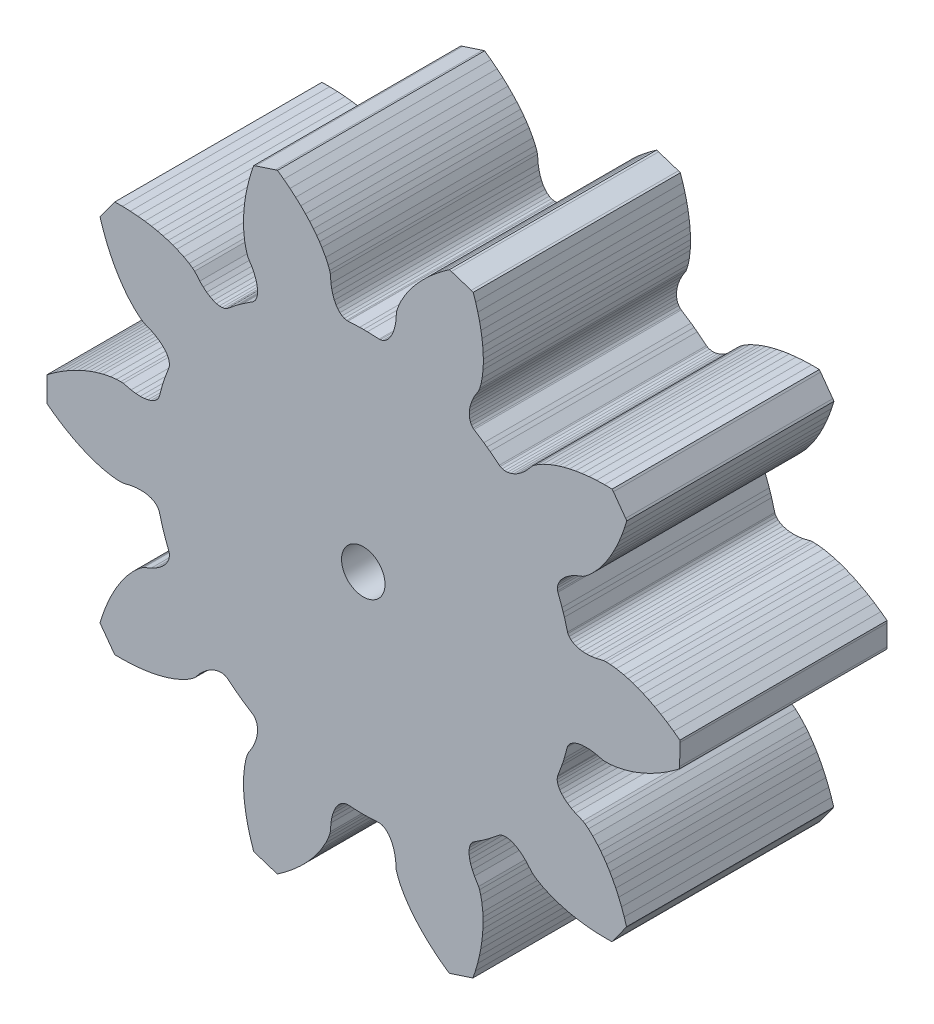
SolidWorks part; units mm, degrees
ref_plane "Front Plane" through (0, 0, 0) normal (0, 0, 1) x (1, 0, 0)
ref_plane "Top Plane" through (0, 0, 0) normal (0, 1, 0) x (1, 0, 0)
ref_plane "Right Plane" through (0, 0, 0) normal (1, 0, 0) x (0, 0, -1)
sketch "Sketch2" plane through (0, 0, 0) normal (0, 0, 1) x (1, 0, 0)
  line L40 (2.1996, 28.3978) -> (2.6736, 28.0849)
  line L41 (2.1445, 11.1227) -> (2.1761, 11.1489)
  line L42 (2.1761, 11.1489) -> (2.1872, 11.1558)
  line L43 (-3.1458, 20.8269) -> (-3.1458, 18.7268) construction
  line L699 (-2.0958, 19.7768) -> (-2.0958, 19.5922) construction
  line L700 (-2.0958, 19.5922) -> (-2.4045, 19.0354) construction
  line L701 (-2.4045, 19.0354) -> (-2.9612, 18.7268) construction
  line L702 (-2.9612, 18.7268) -> (-3.1458, 18.7268) construction
  line L703 (-3.1458, 18.7268) -> (-3.3319, 18.7268) construction
  line L704 (-3.3319, 18.7268) -> (-3.8886, 19.0354) construction
  line L705 (-3.8886, 19.0354) -> (-4.1959, 19.5922) construction
  line L706 (-4.1959, 19.5922) -> (-4.1959, 19.7768) construction
  line L707 (-4.1959, 19.7768) -> (-4.1959, 19.9628) construction
  line L708 (-4.1959, 19.9628) -> (-3.8886, 20.5196) construction
  line L709 (-3.8886, 20.5196) -> (-3.3319, 20.8269) construction
  line L710 (-3.3319, 20.8269) -> (-3.1458, 20.8269) construction
  line L711 (-3.1458, 20.8269) -> (-2.9612, 20.8269) construction
  line L712 (-2.9612, 20.8269) -> (-2.4045, 20.5196) construction
  line L713 (-2.4045, 20.5196) -> (-2.0958, 19.9628) construction
  line L714 (-2.0958, 19.9628) -> (-2.0958, 19.7768) construction
  line L715 (9.572, 28.2627) -> (9.4604, 27.9073)
  line L716 (9.4604, 27.9073) -> (9.3309, 27.5489)
  line L717 (9.3309, 27.5489) -> (9.1945, 27.2141)
  line L718 (9.1945, 27.2141) -> (9.0538, 26.9068)
  line L719 (9.0538, 26.9068) -> (8.9077, 26.6215)
  line L720 (8.9077, 26.6215) -> (8.7617, 26.3625)
  line L721 (8.7617, 26.3625) -> (8.6144, 26.1254)
  line L722 (8.6144, 26.1254) -> (8.4696, 25.9132)
  line L723 (8.4696, 25.9132) -> (8.3291, 25.723)
  line L724 (8.3291, 25.723) -> (8.194, 25.5563)
  line L725 (8.194, 25.5563) -> (7.9433, 25.2834)
  line L726 (7.9433, 25.2834) -> (7.731, 25.0878)
  line L727 (7.731, 25.0878) -> (7.5684, 24.961)
  line L728 (7.5684, 24.961) -> (7.4638, 24.8921)
  line L729 (7.4638, 24.8921) -> (7.1082, 24.746)
  line L730 (7.1082, 24.746) -> (6.9029, 24.6385)
  line L731 (6.9029, 24.6385) -> (6.7236, 24.5214)
  line L732 (6.7236, 24.5214) -> (6.572, 24.4001)
  line L733 (6.572, 24.4001) -> (6.448, 24.2747)
  line L734 (6.448, 24.2747) -> (6.3515, 24.148)
  line L735 (6.3515, 24.148) -> (6.2814, 24.0226)
  line L736 (6.2814, 24.0226) -> (6.2387, 23.8985)
  line L737 (6.2387, 23.8985) -> (6.2235, 23.7814)
  line L738 (6.2235, 23.7814) -> (6.2331, 23.6698)
  line L739 (6.2331, 23.6698) -> (6.2481, 23.6174)
  line L740 (6.2481, 23.6174) -> (6.244, 23.6298)
  line L741 (6.244, 23.6298) -> (6.2481, 23.616)
  line L742 (6.2481, 23.616) -> (6.4467, 23.0854)
  line L743 (6.4467, 23.0854) -> (6.5059, 22.9091)
  line L744 (6.5059, 22.9091) -> (6.5623, 22.7327)
  line L745 (6.5623, 22.7327) -> (6.7127, 22.1843)
  line L746 (6.7127, 22.1843) -> (6.7167, 22.1718)
  line L747 (6.7167, 22.1718) -> (6.7139, 22.1843)
  line L748 (6.7139, 22.1843) -> (6.732, 22.1333)
  line L749 (6.732, 22.1333) -> (6.7899, 22.0382)
  line L750 (6.7899, 22.0382) -> (6.8724, 21.9514)
  line L751 (6.8724, 21.9514) -> (6.9786, 21.8769)
  line L752 (6.9786, 21.8769) -> (7.1094, 21.8163)
  line L753 (7.1094, 21.8163) -> (7.2626, 21.7695)
  line L754 (7.2626, 21.7695) -> (7.4361, 21.7419)
  line L755 (7.4361, 21.7419) -> (7.6304, 21.7322)
  line L756 (7.6304, 21.7322) -> (7.8427, 21.7433)
  line L757 (7.8427, 21.7433) -> (8.0741, 21.7763)
  line L758 (8.0741, 21.7763) -> (8.4475, 21.8673)
  line L759 (8.4475, 21.8673) -> (8.5717, 21.8728)
  line L760 (8.5717, 21.8728) -> (8.7769, 21.8659)
  line L761 (8.7769, 21.8659) -> (9.0637, 21.8328)
  line L762 (9.0637, 21.8328) -> (9.4274, 21.7598)
  line L763 (9.4274, 21.7598) -> (9.6342, 21.7033)
  line L764 (9.6342, 21.7033) -> (9.86, 21.6331)
  line L765 (9.86, 21.6331) -> (10.1026, 21.5462)
  line L766 (10.1026, 21.5462) -> (10.3604, 21.4415)
  line L767 (10.3604, 21.4415) -> (10.6319, 21.3175)
  line L768 (10.6319, 21.3175) -> (10.9171, 21.1714)
  line L769 (10.9171, 21.1714) -> (11.212, 21.006)
  line L770 (11.212, 21.006) -> (11.5191, 20.8158)
  line L771 (11.5191, 20.8158) -> (11.8336, 20.6023)
  line L772 (11.8336, 20.6023) -> (12.1338, 20.3804)
  line L773 (12.1338, 20.3804) -> (12.1366, 20.2798)
  line L774 (12.1366, 20.2798) -> (12.1242, 19.2752)
  line L775 (12.1242, 19.2752) -> (12.1214, 19.1746)
  line L776 (12.1214, 19.1746) -> (11.8212, 18.9514)
  line L777 (11.8212, 18.9514) -> (11.5067, 18.7378)
  line L778 (11.5067, 18.7378) -> (11.1996, 18.5476)
  line L779 (11.1996, 18.5476) -> (10.9047, 18.3822)
  line L780 (10.9047, 18.3822) -> (10.6195, 18.2361)
  line L781 (10.6195, 18.2361) -> (10.348, 18.1135)
  line L782 (10.348, 18.1135) -> (10.0902, 18.0074)
  line L783 (10.0902, 18.0074) -> (9.8476, 17.9206)
  line L784 (9.8476, 17.9206) -> (9.6218, 17.8503)
  line L785 (9.6218, 17.8503) -> (9.415, 17.7952)
  line L786 (9.415, 17.7952) -> (9.0513, 17.7208)
  line L787 (9.0513, 17.7208) -> (8.7645, 17.6877)
  line L788 (8.7645, 17.6877) -> (8.5593, 17.6808)
  line L789 (8.5593, 17.6808) -> (8.4351, 17.6863)
  line L790 (8.4351, 17.6863) -> (8.0617, 17.7773)
  line L791 (8.0617, 17.7773) -> (7.8303, 17.8104)
  line L792 (7.8303, 17.8104) -> (7.618, 17.8214)
  line L793 (7.618, 17.8214) -> (7.4237, 17.8117)
  line L794 (7.4237, 17.8117) -> (7.2502, 17.7842)
  line L795 (7.2502, 17.7842) -> (7.097, 17.7387)
  line L796 (7.097, 17.7387) -> (6.9662, 17.6767)
  line L797 (6.9662, 17.6767) -> (6.86, 17.6023)
  line L798 (6.86, 17.6023) -> (6.7775, 17.5168)
  line L799 (6.7775, 17.5168) -> (6.7196, 17.4203)
  line L800 (6.7196, 17.4203) -> (6.7015, 17.3694)
  line L801 (6.7015, 17.3694) -> (6.7043, 17.3818)
  line L802 (6.7043, 17.3818) -> (6.7003, 17.3694)
  line L803 (6.7003, 17.3694) -> (6.5499, 16.8223)
  line L804 (6.5499, 16.8223) -> (6.4935, 16.6445)
  line L805 (6.4935, 16.6445) -> (6.4343, 16.4695)
  line L806 (6.4343, 16.4695) -> (6.2357, 15.9376)
  line L807 (6.2357, 15.9376) -> (6.2316, 15.9238)
  line L808 (6.2316, 15.9238) -> (6.2357, 15.9362)
  line L809 (6.2357, 15.9362) -> (6.2207, 15.8852)
  line L810 (6.2207, 15.8852) -> (6.2111, 15.7736)
  line L811 (6.2111, 15.7736) -> (6.2263, 15.6551)
  line L812 (6.2263, 15.6551) -> (6.269, 15.5311)
  line L813 (6.269, 15.5311) -> (6.3391, 15.4057)
  line L814 (6.3391, 15.4057) -> (6.4356, 15.2789)
  line L815 (6.4356, 15.2789) -> (6.5596, 15.1535)
  line L816 (6.5596, 15.1535) -> (6.7112, 15.0322)
  line L817 (6.7112, 15.0322) -> (6.8905, 14.9165)
  line L818 (6.8905, 14.9165) -> (7.0958, 14.8076)
  line L819 (7.0958, 14.8076) -> (7.4514, 14.6615)
  line L820 (7.4514, 14.6615) -> (7.556, 14.5926)
  line L821 (7.556, 14.5926) -> (7.7186, 14.4658)
  line L822 (7.7186, 14.4658) -> (7.9309, 14.2715)
  line L823 (7.9309, 14.2715) -> (8.1816, 13.9973)
  line L824 (8.1816, 13.9973) -> (8.3167, 13.8306)
  line L825 (8.3167, 13.8306) -> (8.4572, 13.6404)
  line L826 (8.4572, 13.6404) -> (8.602, 13.4282)
  line L827 (8.602, 13.4282) -> (8.7493, 13.1912)
  line L828 (8.7493, 13.1912) -> (8.8953, 12.9321)
  line L829 (8.8953, 12.9321) -> (9.0414, 12.6468)
  line L830 (9.0414, 12.6468) -> (9.1821, 12.3395)
  line L831 (9.1821, 12.3395) -> (9.3185, 12.0047)
  line L832 (9.3185, 12.0047) -> (9.448, 11.6478)
  line L833 (9.448, 11.6478) -> (9.5596, 11.2908)
  line L834 (9.5596, 11.2908) -> (9.5032, 11.2082)
  line L835 (9.5032, 11.2082) -> (8.9134, 10.3951)
  line L836 (8.9134, 10.3951) -> (8.8514, 10.3152)
  line L837 (8.8514, 10.3152) -> (8.478, 10.3125)
  line L838 (8.478, 10.3125) -> (8.0975, 10.3235)
  line L839 (8.0975, 10.3235) -> (7.7366, 10.351)
  line L840 (7.7366, 10.351) -> (7.4016, 10.3896)
  line L841 (7.4016, 10.3896) -> (7.0848, 10.4406)
  line L842 (7.0848, 10.4406) -> (6.794, 10.4985)
  line L843 (6.794, 10.4985) -> (6.5225, 10.566)
  line L844 (6.5225, 10.566) -> (6.2758, 10.6377)
  line L845 (6.2758, 10.6377) -> (6.0513, 10.7134)
  line L846 (6.0513, 10.7134) -> (5.8499, 10.7906)
  line L847 (5.8499, 10.7906) -> (5.5138, 10.9436)
  line L848 (5.5138, 10.9436) -> (5.2616, 11.0855)
  line L849 (5.2616, 11.0855) -> (5.0907, 11.2013)
  line L850 (5.0907, 11.2013) -> (4.9942, 11.2784)
  line L851 (4.9942, 11.2784) -> (4.7463, 11.572)
  line L852 (4.7463, 11.572) -> (4.5781, 11.7346)
  line L853 (4.5781, 11.7346) -> (4.4127, 11.8683)
  line L854 (4.4127, 11.8683) -> (4.2501, 11.9743)
  line L855 (4.2501, 11.9743) -> (4.093, 12.0543)
  line L856 (4.093, 12.0543) -> (3.9428, 12.1066)
  line L857 (3.9428, 12.1066) -> (3.8008, 12.1342)
  line L858 (3.8008, 12.1342) -> (3.6713, 12.137)
  line L859 (3.6713, 12.137) -> (3.5528, 12.1149)
  line L860 (3.5528, 12.1149) -> (3.4508, 12.0708)
  line L861 (3.4508, 12.0708) -> (3.4054, 12.0405)
  line L862 (3.4054, 12.0405) -> (3.415, 12.0488)
  line L863 (3.415, 12.0488) -> (3.404, 12.0419)
  line L864 (3.404, 12.0419) -> (2.9603, 11.6877)
  line L865 (2.9603, 11.6877) -> (2.8114, 11.5761)
  line L866 (2.8114, 11.5761) -> (2.6612, 11.4686)
  line L867 (2.6612, 11.4686) -> (2.1872, 11.1558)
  line L871 (2.1445, 11.1227) -> (2.07, 11.0387)
  line L872 (2.07, 11.0387) -> (2.0135, 10.9325)
  line L873 (2.0135, 10.9325) -> (1.9763, 10.8085)
  line L874 (1.9763, 10.8085) -> (1.9584, 10.6652)
  line L875 (1.9584, 10.6652) -> (1.9625, 10.5068)
  line L876 (1.9625, 10.5068) -> (1.9887, 10.3317)
  line L877 (1.9887, 10.3317) -> (2.0397, 10.1443)
  line L878 (2.0397, 10.1443) -> (2.1169, 9.9445)
  line L879 (2.1169, 9.9445) -> (2.2189, 9.7364)
  line L880 (2.2189, 9.7364) -> (2.42, 9.4084)
  line L881 (2.42, 9.4084) -> (2.4655, 9.2927)
  line L882 (2.4655, 9.2927) -> (2.522, 9.0943)
  line L883 (2.522, 9.0943) -> (2.5785, 8.8118)
  line L884 (2.5785, 8.8118) -> (2.6212, 8.4438)
  line L885 (2.6212, 8.4438) -> (2.6323, 8.2302)
  line L886 (2.6323, 8.2302) -> (2.635, 7.9918)
  line L887 (2.635, 7.9918) -> (2.6268, 7.7355)
  line L888 (2.6268, 7.7355) -> (2.6061, 7.4572)
  line L889 (2.6061, 7.4572) -> (2.573, 7.1622)
  line L890 (2.573, 7.1622) -> (2.522, 6.8453)
  line L891 (2.522, 6.8453) -> (2.4559, 6.5132)
  line L892 (2.4559, 6.5132) -> (2.3704, 6.1632)
  line L893 (2.3704, 6.1632) -> (2.2643, 5.798)
  line L894 (2.2643, 5.798) -> (2.1458, 5.4438)
  line L895 (2.1458, 5.4438) -> (2.0507, 5.4094)
  line L896 (2.0507, 5.4094) -> (1.0944, 5.098)
  line L897 (1.0944, 5.098) -> (0.9979, 5.0704)
  line L898 (0.9979, 5.0704) -> (0.6948, 5.2881)
  line L899 (0.6948, 5.2881) -> (0.3943, 5.521)
  line L900 (0.3943, 5.521) -> (0.1174, 5.7539)
  line L901 (0.1174, 5.7539) -> (-0.1307, 5.9827)
  line L902 (-0.1307, 5.9827) -> (-0.3567, 6.21)
  line L903 (-0.3567, 6.21) -> (-0.5579, 6.4291)
  line L904 (-0.5579, 6.4291) -> (-0.7384, 6.6414)
  line L905 (-0.7384, 6.6414) -> (-0.8955, 6.8453)
  line L906 (-0.8955, 6.8453) -> (-1.0333, 7.0382)
  line L907 (-1.0333, 7.0382) -> (-1.1505, 7.2188)
  line L908 (-1.1505, 7.2188) -> (-1.3323, 7.5412)
  line L909 (-1.3323, 7.5412) -> (-1.4522, 7.803)
  line L910 (-1.4522, 7.803) -> (-1.5225, 7.9973)
  line L911 (-1.5225, 7.9973) -> (-1.5556, 8.1172)
  line L912 (-1.5556, 8.1172) -> (-1.5845, 8.5003)
  line L913 (-1.5845, 8.5003) -> (-1.6245, 8.7291)
  line L914 (-1.6245, 8.7291) -> (-1.6796, 8.9358)
  line L915 (-1.6796, 8.9358) -> (-1.7485, 9.1177)
  line L916 (-1.7485, 9.1177) -> (-1.8298, 9.2748)
  line L917 (-1.8298, 9.2748) -> (-1.9194, 9.4057)
  line L918 (-1.9194, 9.4057) -> (-2.0186, 9.5104)
  line L919 (-2.0186, 9.5104) -> (-2.122, 9.589)
  line L920 (-2.122, 9.589) -> (-2.2294, 9.6414)
  line L921 (-2.2294, 9.6414) -> (-2.3383, 9.6661)
  line L922 (-2.3383, 9.6661) -> (-2.3934, 9.6675)
  line L923 (-2.3934, 9.6675) -> (-2.3797, 9.6689)
  line L924 (-2.3797, 9.6689) -> (-2.3934, 9.6689)
  line L925 (-2.3934, 9.6689) -> (-2.9598, 9.6427)
  line L926 (-2.9598, 9.6427) -> (-3.1458, 9.6414)
  line L927 (-3.1458, 9.6414) -> (-3.3319, 9.6427)
  line L928 (-3.3319, 9.6427) -> (-3.8982, 9.6689)
  line L929 (-3.8982, 9.6689) -> (-3.912, 9.6689)
  line L930 (-3.912, 9.6689) -> (-3.8996, 9.6675)
  line L931 (-3.8996, 9.6675) -> (-3.9534, 9.6661)
  line L932 (-3.9534, 9.6661) -> (-4.0622, 9.6414)
  line L933 (-4.0622, 9.6414) -> (-4.1697, 9.589)
  line L934 (-4.1697, 9.589) -> (-4.2745, 9.5104)
  line L935 (-4.2745, 9.5104) -> (-4.3723, 9.4057)
  line L936 (-4.3723, 9.4057) -> (-4.4633, 9.2748)
  line L937 (-4.4633, 9.2748) -> (-4.5432, 9.1177)
  line L938 (-4.5432, 9.1177) -> (-4.6121, 8.9358)
  line L939 (-4.6121, 8.9358) -> (-4.6672, 8.7291)
  line L940 (-4.6672, 8.7291) -> (-4.7072, 8.5003)
  line L941 (-4.7072, 8.5003) -> (-4.7361, 8.1172)
  line L942 (-4.7361, 8.1172) -> (-4.7692, 7.9973)
  line L943 (-4.7692, 7.9973) -> (-4.8395, 7.803)
  line L944 (-4.8395, 7.803) -> (-4.9594, 7.5412)
  line L945 (-4.9594, 7.5412) -> (-5.1426, 7.2188)
  line L946 (-5.1426, 7.2188) -> (-5.2584, 7.0382)
  line L947 (-5.2584, 7.0382) -> (-5.3962, 6.8453)
  line L948 (-5.3962, 6.8453) -> (-5.5533, 6.6414)
  line L949 (-5.5533, 6.6414) -> (-5.7338, 6.4291)
  line L950 (-5.7338, 6.4291) -> (-5.935, 6.21)
  line L951 (-5.935, 6.21) -> (-6.161, 5.9827)
  line L952 (-6.161, 5.9827) -> (-6.4104, 5.7539)
  line L953 (-6.4104, 5.7539) -> (-6.686, 5.521)
  line L954 (-6.686, 5.521) -> (-6.9864, 5.2881)
  line L955 (-6.9864, 5.2881) -> (-7.2896, 5.0704)
  line L956 (-7.2896, 5.0704) -> (-7.3875, 5.098)
  line L957 (-7.3875, 5.098) -> (-8.3438, 5.4094)
  line L958 (-8.3438, 5.4094) -> (-8.4375, 5.4438)
  line L959 (-8.4375, 5.4438) -> (-8.556, 5.798)
  line L960 (-8.556, 5.798) -> (-8.6621, 6.1632)
  line L961 (-8.6621, 6.1632) -> (-8.7475, 6.5132)
  line L962 (-8.7475, 6.5132) -> (-8.8151, 6.8453)
  line L963 (-8.8151, 6.8453) -> (-8.8647, 7.1622)
  line L964 (-8.8647, 7.1622) -> (-8.8992, 7.4572)
  line L965 (-8.8992, 7.4572) -> (-8.9184, 7.7355)
  line L966 (-8.9184, 7.7355) -> (-8.9267, 7.9918)
  line L967 (-8.9267, 7.9918) -> (-8.9239, 8.2302)
  line L968 (-8.9239, 8.2302) -> (-8.913, 8.4438)
  line L969 (-8.913, 8.4438) -> (-8.8702, 8.8118)
  line L970 (-8.8702, 8.8118) -> (-8.8137, 9.0943)
  line L971 (-8.8137, 9.0943) -> (-8.7572, 9.2927)
  line L972 (-8.7572, 9.2927) -> (-8.7131, 9.4084)
  line L973 (-8.7131, 9.4084) -> (-8.5106, 9.7364)
  line L974 (-8.5106, 9.7364) -> (-8.4086, 9.9445)
  line L975 (-8.4086, 9.9445) -> (-8.3314, 10.1443)
  line L976 (-8.3314, 10.1443) -> (-8.2804, 10.3317)
  line L977 (-8.2804, 10.3317) -> (-8.2542, 10.5068)
  line L978 (-8.2542, 10.5068) -> (-8.2501, 10.6652)
  line L979 (-8.2501, 10.6652) -> (-8.268, 10.8085)
  line L980 (-8.268, 10.8085) -> (-8.3052, 10.9325)
  line L981 (-8.3052, 10.9325) -> (-8.3617, 11.0387)
  line L982 (-8.3617, 11.0387) -> (-8.4361, 11.1227)
  line L983 (-8.4361, 11.1227) -> (-8.4788, 11.1558)
  line L986 (-8.4788, 11.1558) -> (-8.9529, 11.4686)
  line L987 (-8.9529, 11.4686) -> (-9.1031, 11.5761)
  line L988 (-9.1031, 11.5761) -> (-9.2533, 11.6877)
  line L989 (-9.2533, 11.6877) -> (-9.697, 12.0419)
  line L990 (-9.697, 12.0419) -> (-9.7081, 12.0488)
  line L991 (-9.7081, 12.0488) -> (-9.697, 12.0405)
  line L992 (-9.697, 12.0405) -> (-9.7425, 12.0708)
  line L993 (-9.7425, 12.0708) -> (-9.8445, 12.1149)
  line L994 (-9.8445, 12.1149) -> (-9.963, 12.137)
  line L995 (-9.963, 12.137) -> (-10.0925, 12.1342)
  line L996 (-10.0925, 12.1342) -> (-10.2345, 12.1066)
  line L997 (-10.2345, 12.1066) -> (-10.3847, 12.0543)
  line L998 (-10.3847, 12.0543) -> (-10.5418, 11.9743)
  line L999 (-10.5418, 11.9743) -> (-10.7044, 11.8683)
  line L1000 (-10.7044, 11.8683) -> (-10.8711, 11.7346)
  line L1001 (-10.8711, 11.7346) -> (-11.0379, 11.572)
  line L1002 (-11.0379, 11.572) -> (-11.2859, 11.2784)
  line L1003 (-11.2859, 11.2784) -> (-11.3838, 11.2013)
  line L1004 (-11.3838, 11.2013) -> (-11.5547, 11.0855)
  line L1005 (-11.5547, 11.0855) -> (-11.8054, 10.9436)
  line L1006 (-11.8054, 10.9436) -> (-12.143, 10.7906)
  line L1007 (-12.143, 10.7906) -> (-12.3429, 10.7134)
  line L1008 (-12.3429, 10.7134) -> (-12.5675, 10.6377)
  line L1009 (-12.5675, 10.6377) -> (-12.8142, 10.566)
  line L1010 (-12.8142, 10.566) -> (-13.0856, 10.4985)
  line L1011 (-13.0856, 10.4985) -> (-13.3764, 10.4406)
  line L1012 (-13.3764, 10.4406) -> (-13.6934, 10.3896)
  line L1013 (-13.6934, 10.3896) -> (-14.0282, 10.351)
  line L1014 (-14.0282, 10.351) -> (-14.3892, 10.3235)
  line L1015 (-14.3892, 10.3235) -> (-14.7696, 10.3125)
  line L1016 (-14.7696, 10.3125) -> (-15.143, 10.3152)
  line L1017 (-15.143, 10.3152) -> (-15.205, 10.3951)
  line L1018 (-15.205, 10.3951) -> (-15.7962, 11.2082)
  line L1019 (-15.7962, 11.2082) -> (-15.8514, 11.2908)
  line L1020 (-15.8514, 11.2908) -> (-15.7397, 11.6478)
  line L1021 (-15.7397, 11.6478) -> (-15.6102, 12.0047)
  line L1022 (-15.6102, 12.0047) -> (-15.4738, 12.3395)
  line L1023 (-15.4738, 12.3395) -> (-15.3332, 12.6468)
  line L1024 (-15.3332, 12.6468) -> (-15.1871, 12.9321)
  line L1025 (-15.1871, 12.9321) -> (-15.0411, 13.1912)
  line L1026 (-15.0411, 13.1912) -> (-14.8936, 13.4282)
  line L1027 (-14.8936, 13.4282) -> (-14.7489, 13.6404)
  line L1028 (-14.7489, 13.6404) -> (-14.6084, 13.8306)
  line L1029 (-14.6084, 13.8306) -> (-14.4733, 13.9973)
  line L1030 (-14.4733, 13.9973) -> (-14.2225, 14.2715)
  line L1031 (-14.2225, 14.2715) -> (-14.0103, 14.4658)
  line L1032 (-14.0103, 14.4658) -> (-13.8477, 14.5926)
  line L1033 (-13.8477, 14.5926) -> (-13.743, 14.6615)
  line L1034 (-13.743, 14.6615) -> (-13.3888, 14.8076)
  line L1035 (-13.3888, 14.8076) -> (-13.1821, 14.9165)
  line L1036 (-13.1821, 14.9165) -> (-13.0029, 15.0322)
  line L1037 (-13.0029, 15.0322) -> (-12.8513, 15.1535)
  line L1038 (-12.8513, 15.1535) -> (-12.7273, 15.2789)
  line L1039 (-12.7273, 15.2789) -> (-12.6309, 15.4057)
  line L1040 (-12.6309, 15.4057) -> (-12.5606, 15.5311)
  line L1041 (-12.5606, 15.5311) -> (-12.5192, 15.6551)
  line L1042 (-12.5192, 15.6551) -> (-12.5027, 15.7736)
  line L1043 (-12.5027, 15.7736) -> (-12.5124, 15.8852)
  line L1044 (-12.5124, 15.8852) -> (-12.5275, 15.9362)
  line L1045 (-12.5275, 15.9362) -> (-12.5234, 15.9238)
  line L1046 (-12.5234, 15.9238) -> (-12.5275, 15.9376)
  line L1047 (-12.5275, 15.9376) -> (-12.7273, 16.4695)
  line L1048 (-12.7273, 16.4695) -> (-12.7852, 16.6445)
  line L1049 (-12.7852, 16.6445) -> (-12.8417, 16.8223)
  line L1050 (-12.8417, 16.8223) -> (-12.9919, 17.3694)
  line L1051 (-12.9919, 17.3694) -> (-12.9961, 17.3818)
  line L1052 (-12.9961, 17.3818) -> (-12.9933, 17.3694)
  line L1053 (-12.9933, 17.3694) -> (-13.0112, 17.4203)
  line L1054 (-13.0112, 17.4203) -> (-13.0691, 17.5168)
  line L1055 (-13.0691, 17.5168) -> (-13.1518, 17.6023)
  line L1056 (-13.1518, 17.6023) -> (-13.2579, 17.6767)
  line L1057 (-13.2579, 17.6767) -> (-13.3888, 17.7387)
  line L1058 (-13.3888, 17.7387) -> (-13.5418, 17.7842)
  line L1059 (-13.5418, 17.7842) -> (-13.7154, 17.8117)
  line L1060 (-13.7154, 17.8117) -> (-13.9097, 17.8214)
  line L1061 (-13.9097, 17.8214) -> (-14.1233, 17.8104)
  line L1062 (-14.1233, 17.8104) -> (-14.3535, 17.7773)
  line L1063 (-14.3535, 17.7773) -> (-14.7269, 17.6863)
  line L1064 (-14.7269, 17.6863) -> (-14.8509, 17.6808)
  line L1065 (-14.8509, 17.6808) -> (-15.0576, 17.6877)
  line L1066 (-15.0576, 17.6877) -> (-15.3428, 17.7208)
  line L1067 (-15.3428, 17.7208) -> (-15.7067, 17.7952)
  line L1068 (-15.7067, 17.7952) -> (-15.9134, 17.8503)
  line L1069 (-15.9134, 17.8503) -> (-16.1407, 17.9206)
  line L1070 (-16.1407, 17.9206) -> (-16.3819, 18.0074)
  line L1071 (-16.3819, 18.0074) -> (-16.641, 18.1135)
  line L1072 (-16.641, 18.1135) -> (-16.9111, 18.2361)
  line L1073 (-16.9111, 18.2361) -> (-17.1963, 18.3822)
  line L1074 (-17.1963, 18.3822) -> (-17.4912, 18.5476)
  line L1075 (-17.4912, 18.5476) -> (-17.7985, 18.7378)
  line L1076 (-17.7985, 18.7378) -> (-18.1127, 18.9514)
  line L1077 (-18.1127, 18.9514) -> (-18.4131, 19.1746)
  line L1078 (-18.4131, 19.1746) -> (-18.4173, 19.2752)
  line L1079 (-18.4173, 19.2752) -> (-18.4173, 20.2798)
  line L1080 (-18.4173, 20.2798) -> (-18.4131, 20.3804)
  line L1081 (-18.4131, 20.3804) -> (-18.1127, 20.6023)
  line L1082 (-18.1127, 20.6023) -> (-17.7985, 20.8158)
  line L1083 (-17.7985, 20.8158) -> (-17.4912, 21.006)
  line L1084 (-17.4912, 21.006) -> (-17.1963, 21.1714)
  line L1085 (-17.1963, 21.1714) -> (-16.9111, 21.3175)
  line L1086 (-16.9111, 21.3175) -> (-16.641, 21.4415)
  line L1087 (-16.641, 21.4415) -> (-16.3819, 21.5462)
  line L1088 (-16.3819, 21.5462) -> (-16.1407, 21.6331)
  line L1089 (-16.1407, 21.6331) -> (-15.9134, 21.7033)
  line L1090 (-15.9134, 21.7033) -> (-15.7067, 21.7598)
  line L1091 (-15.7067, 21.7598) -> (-15.3428, 21.8328)
  line L1092 (-15.3428, 21.8328) -> (-15.0576, 21.8659)
  line L1093 (-15.0576, 21.8659) -> (-14.8509, 21.8728)
  line L1094 (-14.8509, 21.8728) -> (-14.7269, 21.8673)
  line L1095 (-14.7269, 21.8673) -> (-14.3535, 21.7763)
  line L1096 (-14.3535, 21.7763) -> (-14.1233, 21.7433)
  line L1097 (-14.1233, 21.7433) -> (-13.9097, 21.7322)
  line L1098 (-13.9097, 21.7322) -> (-13.7154, 21.7419)
  line L1099 (-13.7154, 21.7419) -> (-13.5418, 21.7695)
  line L1100 (-13.5418, 21.7695) -> (-13.3888, 21.8163)
  line L1101 (-13.3888, 21.8163) -> (-13.2579, 21.8769)
  line L1102 (-13.2579, 21.8769) -> (-13.1518, 21.9514)
  line L1103 (-13.1518, 21.9514) -> (-13.0691, 22.0382)
  line L1104 (-13.0691, 22.0382) -> (-13.0112, 22.1333)
  line L1105 (-13.0112, 22.1333) -> (-12.9933, 22.1843)
  line L1106 (-12.9933, 22.1843) -> (-12.9961, 22.1718)
  line L1107 (-12.9961, 22.1718) -> (-12.9919, 22.1843)
  line L1108 (-12.9919, 22.1843) -> (-12.8417, 22.7327)
  line L1109 (-12.8417, 22.7327) -> (-12.7852, 22.9091)
  line L1110 (-12.7852, 22.9091) -> (-12.7273, 23.0854)
  line L1111 (-12.7273, 23.0854) -> (-12.5275, 23.616)
  line L1112 (-12.5275, 23.616) -> (-12.5234, 23.6298)
  line L1113 (-12.5234, 23.6298) -> (-12.5275, 23.6174)
  line L1114 (-12.5275, 23.6174) -> (-12.5124, 23.6698)
  line L1115 (-12.5124, 23.6698) -> (-12.5027, 23.7814)
  line L1116 (-12.5027, 23.7814) -> (-12.5192, 23.8985)
  line L1117 (-12.5192, 23.8985) -> (-12.5606, 24.0226)
  line L1118 (-12.5606, 24.0226) -> (-12.6309, 24.148)
  line L1119 (-12.6309, 24.148) -> (-12.7273, 24.2747)
  line L1120 (-12.7273, 24.2747) -> (-12.8513, 24.4001)
  line L1121 (-12.8513, 24.4001) -> (-13.0029, 24.5214)
  line L1122 (-13.0029, 24.5214) -> (-13.1821, 24.6385)
  line L1123 (-13.1821, 24.6385) -> (-13.3888, 24.746)
  line L1124 (-13.3888, 24.746) -> (-13.743, 24.8921)
  line L1125 (-13.743, 24.8921) -> (-13.8477, 24.961)
  line L1126 (-13.8477, 24.961) -> (-14.0103, 25.0878)
  line L1127 (-14.0103, 25.0878) -> (-14.2225, 25.2834)
  line L1128 (-14.2225, 25.2834) -> (-14.4733, 25.5563)
  line L1129 (-14.4733, 25.5563) -> (-14.6084, 25.723)
  line L1130 (-14.6084, 25.723) -> (-14.7489, 25.9132)
  line L1131 (-14.7489, 25.9132) -> (-14.8936, 26.1254)
  line L1132 (-14.8936, 26.1254) -> (-15.0411, 26.3625)
  line L1133 (-15.0411, 26.3625) -> (-15.1871, 26.6215)
  line L1134 (-15.1871, 26.6215) -> (-15.3332, 26.9068)
  line L1135 (-15.3332, 26.9068) -> (-15.4738, 27.2141)
  line L1136 (-15.4738, 27.2141) -> (-15.6102, 27.5489)
  line L1137 (-15.6102, 27.5489) -> (-15.7397, 27.9073)
  line L1138 (-15.7397, 27.9073) -> (-15.8514, 28.2627)
  line L1139 (-15.8514, 28.2627) -> (-15.7962, 28.3468)
  line L1140 (-15.7962, 28.3468) -> (-15.205, 29.1598)
  line L1141 (-15.205, 29.1598) -> (-15.143, 29.2383)
  line L1142 (-15.143, 29.2383) -> (-14.7696, 29.2426)
  line L1143 (-14.7696, 29.2426) -> (-14.3892, 29.2302)
  line L1144 (-14.3892, 29.2302) -> (-14.0282, 29.2025)
  line L1145 (-14.0282, 29.2025) -> (-13.6934, 29.1639)
  line L1146 (-13.6934, 29.1639) -> (-13.3764, 29.1143)
  line L1147 (-13.3764, 29.1143) -> (-13.0856, 29.0552)
  line L1148 (-13.0856, 29.0552) -> (-12.8142, 28.9876)
  line L1149 (-12.8142, 28.9876) -> (-12.5675, 28.916)
  line L1150 (-12.5675, 28.916) -> (-12.3429, 28.84)
  line L1151 (-12.3429, 28.84) -> (-12.143, 28.7631)
  line L1152 (-12.143, 28.7631) -> (-11.8054, 28.6102)
  line L1153 (-11.8054, 28.6102) -> (-11.5547, 28.4682)
  line L1154 (-11.5547, 28.4682) -> (-11.3838, 28.3523)
  line L1155 (-11.3838, 28.3523) -> (-11.2859, 28.2751)
  line L1156 (-11.2859, 28.2751) -> (-11.0379, 27.9815)
  line L1157 (-11.0379, 27.9815) -> (-10.8711, 27.8205)
  line L1158 (-10.8711, 27.8205) -> (-10.7044, 27.6853)
  line L1159 (-10.7044, 27.6853) -> (-10.5418, 27.5792)
  line L1160 (-10.5418, 27.5792) -> (-10.3847, 27.4994)
  line L1161 (-10.3847, 27.4994) -> (-10.2345, 27.4471)
  line L1162 (-10.2345, 27.4471) -> (-10.0925, 27.4194)
  line L1163 (-10.0925, 27.4194) -> (-9.963, 27.4166)
  line L1164 (-9.963, 27.4166) -> (-9.8445, 27.4387)
  line L1165 (-9.8445, 27.4387) -> (-9.7425, 27.4829)
  line L1166 (-9.7425, 27.4829) -> (-9.697, 27.5131)
  line L1169 (-9.697, 27.5131) -> (-9.2533, 27.8672)
  line L1170 (-9.2533, 27.8672) -> (-9.1031, 27.9774)
  line L1171 (-9.1031, 27.9774) -> (-8.9529, 28.0849)
  line L1172 (-8.9529, 28.0849) -> (-8.4788, 28.3978)
  line L1175 (-8.4788, 28.3978) -> (-8.4361, 28.4308)
  line L1176 (-8.4361, 28.4308) -> (-8.3617, 28.5164)
  line L1177 (-8.3617, 28.5164) -> (-8.3052, 28.6211)
  line L1178 (-8.3052, 28.6211) -> (-8.268, 28.745)
  line L1179 (-8.268, 28.745) -> (-8.2501, 28.8885)
  line L1180 (-8.2501, 28.8885) -> (-8.2542, 29.0483)
  line L1181 (-8.2542, 29.0483) -> (-8.2804, 29.2218)
  line L1182 (-8.2804, 29.2218) -> (-8.3314, 29.4092)
  line L1183 (-8.3314, 29.4092) -> (-8.4086, 29.6091)
  line L1184 (-8.4086, 29.6091) -> (-8.5106, 29.8172)
  line L1185 (-8.5106, 29.8172) -> (-8.7131, 30.1451)
  line L1186 (-8.7131, 30.1451) -> (-8.7572, 30.2609)
  line L1187 (-8.7572, 30.2609) -> (-8.8137, 30.4593)
  line L1188 (-8.8137, 30.4593) -> (-8.8702, 30.742)
  line L1189 (-8.8702, 30.742) -> (-8.913, 31.1098)
  line L1190 (-8.913, 31.1098) -> (-8.9239, 31.3247)
  line L1191 (-8.9239, 31.3247) -> (-8.9267, 31.5619)
  line L1192 (-8.9267, 31.5619) -> (-8.9184, 31.8182)
  line L1193 (-8.9184, 31.8182) -> (-8.8992, 32.0966)
  line L1194 (-8.8992, 32.0966) -> (-8.8647, 32.3915)
  line L1195 (-8.8647, 32.3915) -> (-8.8151, 32.7084)
  line L1196 (-8.8151, 32.7084) -> (-8.7475, 33.0404)
  line L1197 (-8.7475, 33.0404) -> (-8.6621, 33.3917)
  line L1198 (-8.6621, 33.3917) -> (-8.556, 33.757)
  line L1199 (-8.556, 33.757) -> (-8.4375, 34.1098)
  line L1200 (-8.4375, 34.1098) -> (-8.3438, 34.1456)
  line L1201 (-8.3438, 34.1456) -> (-7.3875, 34.457)
  line L1202 (-7.3875, 34.457) -> (-7.2896, 34.4831)
  line L1203 (-7.2896, 34.4831) -> (-6.9864, 34.267)
  line L1204 (-6.9864, 34.267) -> (-6.686, 34.0325)
  line L1205 (-6.686, 34.0325) -> (-6.4104, 33.7996)
  line L1206 (-6.4104, 33.7996) -> (-6.161, 33.571)
  line L1207 (-6.161, 33.571) -> (-5.935, 33.3437)
  line L1208 (-5.935, 33.3437) -> (-5.7338, 33.1245)
  line L1209 (-5.7338, 33.1245) -> (-5.5533, 32.9122)
  line L1210 (-5.5533, 32.9122) -> (-5.3962, 32.7084)
  line L1211 (-5.3962, 32.7084) -> (-5.2584, 32.5154)
  line L1212 (-5.2584, 32.5154) -> (-5.1426, 32.3348)
  line L1213 (-5.1426, 32.3348) -> (-4.9594, 32.0125)
  line L1214 (-4.9594, 32.0125) -> (-4.8395, 31.7506)
  line L1215 (-4.8395, 31.7506) -> (-4.7692, 31.5563)
  line L1216 (-4.7692, 31.5563) -> (-4.7361, 31.4364)
  line L1217 (-4.7361, 31.4364) -> (-4.7072, 31.0534)
  line L1218 (-4.7072, 31.0534) -> (-4.6672, 30.8245)
  line L1219 (-4.6672, 30.8245) -> (-4.6121, 30.6178)
  line L1220 (-4.6121, 30.6178) -> (-4.5432, 30.4359)
  line L1221 (-4.5432, 30.4359) -> (-4.4633, 30.2789)
  line L1222 (-4.4633, 30.2789) -> (-4.3723, 30.1479)
  line L1223 (-4.3723, 30.1479) -> (-4.2745, 30.0432)
  line L1224 (-4.2745, 30.0432) -> (-4.1697, 29.9647)
  line L1225 (-4.1697, 29.9647) -> (-4.0622, 29.9122)
  line L1226 (-4.0622, 29.9122) -> (-3.9534, 29.8875)
  line L1227 (-3.9534, 29.8875) -> (-3.8996, 29.886)
  line L1229 (-3.8996, 29.886) -> (-3.8858, 29.886)
  line L1230 (-3.8858, 29.886) -> (-3.3195, 29.9109)
  line L1231 (-3.3195, 29.9109) -> (-3.1334, 29.9122)
  line L1232 (-3.1334, 29.9122) -> (-2.9474, 29.9109)
  line L1233 (-2.9474, 29.9109) -> (-2.381, 29.886)
  line L1234 (-2.381, 29.886) -> (-2.3673, 29.886)
  line L1236 (-2.381, 29.886) -> (-2.3259, 29.8875)
  line L1237 (-2.3259, 29.8875) -> (-2.2171, 29.9122)
  line L1238 (-2.2171, 29.9122) -> (-2.1096, 29.9647)
  line L1239 (-2.1096, 29.9647) -> (-2.0062, 30.0432)
  line L1240 (-2.0062, 30.0432) -> (-1.907, 30.1479)
  line L1241 (-1.907, 30.1479) -> (-1.8174, 30.2789)
  line L1242 (-1.8174, 30.2789) -> (-1.7361, 30.4359)
  line L1243 (-1.7361, 30.4359) -> (-1.6672, 30.6178)
  line L1244 (-1.6672, 30.6178) -> (-1.6121, 30.8245)
  line L1245 (-1.6121, 30.8245) -> (-1.5721, 31.0534)
  line L1246 (-1.5721, 31.0534) -> (-1.5432, 31.4364)
  line L1247 (-1.5432, 31.4364) -> (-1.5101, 31.5563)
  line L1248 (-1.5101, 31.5563) -> (-1.4398, 31.7506)
  line L1249 (-1.4398, 31.7506) -> (-1.32, 32.0125)
  line L1250 (-1.32, 32.0125) -> (-1.1381, 32.3348)
  line L1251 (-1.1381, 32.3348) -> (-1.0209, 32.5154)
  line L1252 (-1.0209, 32.5154) -> (-0.8831, 32.7084)
  line L1253 (-0.8831, 32.7084) -> (-0.726, 32.9122)
  line L1254 (-0.726, 32.9122) -> (-0.5455, 33.1245)
  line L1255 (-0.5455, 33.1245) -> (-0.3443, 33.3437)
  line L1256 (-0.3443, 33.3437) -> (-0.1183, 33.571)
  line L1257 (-0.1183, 33.571) -> (0.1298, 33.7996)
  line L1258 (0.1298, 33.7996) -> (0.4067, 34.0325)
  line L1259 (0.4067, 34.0325) -> (0.7071, 34.267)
  line L1260 (0.7071, 34.267) -> (1.0103, 34.4831)
  line L1261 (1.0103, 34.4831) -> (1.1068, 34.457)
  line L1262 (1.1068, 34.457) -> (2.0631, 34.1456)
  line L1263 (2.0631, 34.1456) -> (2.1582, 34.1098)
  line L1264 (2.1582, 34.1098) -> (2.2767, 33.757)
  line L1265 (2.2767, 33.757) -> (2.3828, 33.3917)
  line L1266 (2.3828, 33.3917) -> (2.4683, 33.0404)
  line L1267 (2.4683, 33.0404) -> (2.5344, 32.7084)
  line L1268 (2.5344, 32.7084) -> (2.5854, 32.3915)
  line L1269 (2.5854, 32.3915) -> (2.6185, 32.0966)
  line L1270 (2.6185, 32.0966) -> (2.6392, 31.8182)
  line L1271 (2.6392, 31.8182) -> (2.6474, 31.5619)
  line L1272 (2.6474, 31.5619) -> (2.6447, 31.3247)
  line L1273 (2.6447, 31.3247) -> (2.6336, 31.1098)
  line L1274 (2.6336, 31.1098) -> (2.5909, 30.742)
  line L1275 (2.5909, 30.742) -> (2.5344, 30.4593)
  line L1276 (2.5344, 30.4593) -> (2.4779, 30.2609)
  line L1277 (2.4779, 30.2609) -> (2.4324, 30.1451)
  line L1278 (2.4324, 30.1451) -> (2.2312, 29.8172)
  line L1279 (2.2312, 29.8172) -> (2.1293, 29.6091)
  line L1280 (2.1293, 29.6091) -> (2.0521, 29.4092)
  line L1281 (2.0521, 29.4092) -> (2.0011, 29.2218)
  line L1282 (2.0011, 29.2218) -> (1.9749, 29.0483)
  line L1283 (1.9749, 29.0483) -> (1.9708, 28.8885)
  line L1284 (1.9708, 28.8885) -> (1.9887, 28.745)
  line L1285 (1.9887, 28.745) -> (2.0259, 28.6211)
  line L1286 (2.0259, 28.6211) -> (2.0824, 28.5164)
  line L1287 (2.0824, 28.5164) -> (2.1569, 28.4308)
  line L1288 (2.1569, 28.4308) -> (2.1996, 28.3978)
  line L1292 (2.6736, 28.0849) -> (2.8238, 27.9774)
  line L1293 (2.8238, 27.9774) -> (2.9726, 27.8672)
  line L1294 (2.9726, 27.8672) -> (3.4164, 27.5131)
  line L1295 (3.4164, 27.5131) -> (3.4274, 27.5047)
  line L1296 (3.4274, 27.5047) -> (3.4178, 27.5131)
  line L1297 (3.4178, 27.5131) -> (3.4632, 27.4829)
  line L1298 (3.4632, 27.4829) -> (3.5652, 27.4387)
  line L1299 (3.5652, 27.4387) -> (3.6837, 27.4166)
  line L1300 (3.6837, 27.4166) -> (3.8132, 27.4194)
  line L1301 (3.8132, 27.4194) -> (3.9552, 27.4471)
  line L1302 (3.9552, 27.4471) -> (4.1054, 27.4994)
  line L1303 (4.1054, 27.4994) -> (4.2625, 27.5792)
  line L1304 (4.2625, 27.5792) -> (4.4251, 27.6853)
  line L1305 (4.4251, 27.6853) -> (4.5905, 27.8205)
  line L1306 (4.5905, 27.8205) -> (4.7587, 27.9815)
  line L1307 (4.7587, 27.9815) -> (5.0066, 28.2751)
  line L1308 (5.0066, 28.2751) -> (5.1031, 28.3523)
  line L1309 (5.1031, 28.3523) -> (5.274, 28.4682)
  line L1310 (5.274, 28.4682) -> (5.5262, 28.6102)
  line L1311 (5.5262, 28.6102) -> (5.8623, 28.7631)
  line L1312 (5.8623, 28.7631) -> (6.0637, 28.84)
  line L1313 (6.0637, 28.84) -> (6.2882, 28.916)
  line L1314 (6.2882, 28.916) -> (6.5349, 28.9876)
  line L1315 (6.5349, 28.9876) -> (6.8064, 29.0552)
  line L1316 (6.8064, 29.0552) -> (7.0972, 29.1143)
  line L1317 (7.0972, 29.1143) -> (7.414, 29.1639)
  line L1318 (7.414, 29.1639) -> (7.749, 29.2025)
  line L1319 (7.749, 29.2025) -> (8.1099, 29.2302)
  line L1320 (8.1099, 29.2302) -> (8.4904, 29.2426)
  line L1321 (8.4904, 29.2426) -> (8.8638, 29.2383)
  line L1322 (8.8638, 29.2383) -> (8.9258, 29.1598)
  line L1323 (8.9258, 29.1598) -> (9.5156, 28.3468)
  line L1324 (9.5156, 28.3468) -> (9.572, 28.2627)
  circle A0 centre (-3.1458, 19.7768) radius 1.0501
extrude "Boss-Extrude1" add sketch "Sketch2" along normal blind 10 contours L1324 L1323 L1322 L1321 L1320 L1319 L1318 L1317 L1316 L1315 L1314 L1313 L1312 L1311 L1310 L1309 L1308 L1307 L1306 L1305 L1304 L1303 L1302 L1301 L1300 L1299 L1298 L1297 L1296 L1295 L1294 L1293 L1292 L40 L1288 L1287 L1286 L1285 L1284 L1283 L1282 L1281 L1280 L1279 L1278 L1277 L1276 L1275 L1274 L1273 L1272 region at (2.2029, 27.8874, 0)
